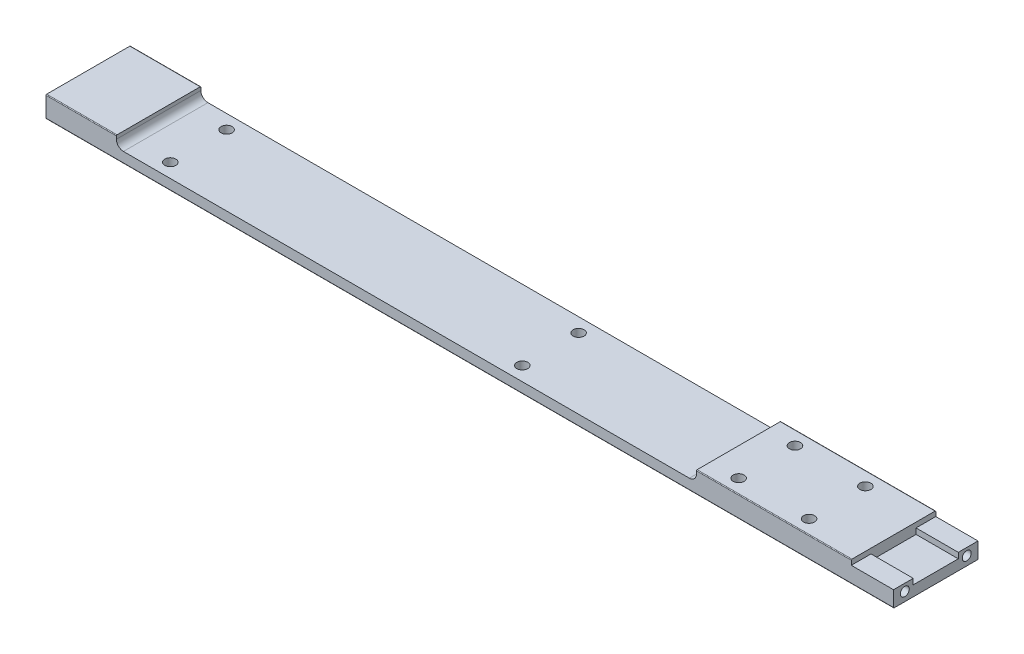
SolidWorks part; units mm, degrees
material "6061 Alloy"
ref_plane "Front Plane" through (0, 0, 0) normal (0, 0, 1) x (1, 0, 0)
ref_plane "Top Plane" through (0, 0, 0) normal (0, 1, 0) x (1, 0, 0)
ref_plane "Right Plane" through (0, 0, 0) normal (1, 0, 0) x (0, 0, -1)
sketch "Sketch1" plane through (0, 0, 0) normal (0, 1, 0) x (1, 0, 0)
  line L1 (191.135, -19.05) -> (-191.135, -19.05)
  line L2 (191.135, -19.05) -> (191.135, 19.05)
  line L3 (191.135, 19.05) -> (-191.135, 19.05)
  line L4 (-191.135, -19.05) -> (-191.135, 19.05)
  line L5 (191.135, -19.05) -> (-191.135, 19.05) construction
  line L6 (191.135, 19.05) -> (-191.135, -19.05) construction
  point P0 (0, 0)
  dimension "Length" = 382.27
  dimension "Width" = 38.1
sketch "Sketch2" plane through (0, 0, 0) normal (1, 0, 0) x (0, 0, -1)
  line L0 (19.05, 4.7625) -> (19.05, -4.7625) construction
  point P2 (19.05, 0)
  dimension "Thickness" = 9.525
sketch "Sketch3" plane through (0, 0, 0) normal (0, 1, 0) x (1, 0, 0)
  line L1 (-191.135, 19.05) -> (191.135, 19.05)
  line L2 (-191.135, 19.05) -> (-191.135, -19.05)
  line L3 (-191.135, -19.05) -> (191.135, -19.05)
  line L4 (191.135, 19.05) -> (191.135, -19.05)
extrude "Boss-Extrude1" add sketch "Sketch3" against normal up to vertex (4.7625 mm away) and the other way up to vertex (4.7625 mm away) up to point (0, -4.7625, -19.05) other way up to point (0, 4.7625, -19.05)
fillet "Fillet1" radius 0.3143 4 edges at (0, -4.7625, 19.05) (0, -4.7625, -19.05) (0, 4.7625, -19.05) (0, 4.7625, 19.05)
sketch "Sketch4" plane through (-191.135, 0, 0) normal (-1, 0, 0) x (0, 0, 1)
  line L0 (0, -0.762) -> (13.97, -0.762) construction
  line L1 (0, -0.762) -> (-13.97, -0.762) construction
  line L2 (0, -0.762) -> (0, 0) construction
  dimension "D1" = 13.97
  dimension "D2" = 13.97
  dimension "D3" = 0.762
hole_wizard "Tap Drill for #10-32 Tap1" positions "Sketch5" profile "Sketch6" hole size "#10-32" standard "ANSI Inch"
sketch "Sketch5" plane through (-191.135, 0, 0) normal (-1, 0, 0) x (0, 0, 1)
  point P0 (-13.97, -0.762)
  point P3 (13.97, -0.762)
sketch "Sketch6" plane through (-191.135, -0.762, -13.97) normal (0, 1, 0) x (0, 0, 1)
  line L0 (0, 0) -> (0, 26.6133)
  line L1 (0, 26.6133) -> (2.0193, 25.4)
  line L2 (2.0193, 25.4) -> (2.0193, 0)
  line L5 (2.0193, 0) -> (0, 0)
  line L10 (0, 26.6133) -> (-2.0193, 25.4) construction
  line L11 (0, -6.35) -> (0, 107.95) construction
  dimension "Hole Dia." = 4.0386
  dimension "Hole Depth" = 25.4
  dimension "Drill Angle" = 118
hole_wizard "Tap Drill for #10-32 Tap2" positions "Sketch7" profile "Sketch8" hole size "#10-32" standard "ANSI Inch"
sketch "Sketch7" plane through (191.135, 0, 0) normal (1, 0, 0) x (0, 0, -1)
  point P0 (-13.97, -0.762)
  point P3 (13.97, -0.762)
sketch "Sketch8" plane through (191.135, -0.762, 13.97) normal (0, 1, 0) x (0, 0, -1)
  line L0 (0, 0) -> (0, 26.6133)
  line L1 (0, 26.6133) -> (2.0193, 25.4)
  line L2 (2.0193, 25.4) -> (2.0193, 0)
  line L5 (2.0193, 0) -> (0, 0)
  line L10 (0, 26.6133) -> (-2.0193, 25.4) construction
  line L11 (0, -6.35) -> (0, 107.95) construction
  dimension "Hole Dia." = 4.0386
  dimension "Hole Depth" = 25.4
  dimension "Drill Angle" = 118
sketch "Sketch10" plane through (0, 0, -19.05) normal (0, 0, -1) x (-1, 0, 0)
  line L0 (159.385, 4.7625) -> (159.385, 3.175)
  line L1 (-191.135, 4.7625) -> (191.135, 4.7625) construction
  line L2 (156.21, 0) -> (-99.06, 0)
  line L3 (-102.235, 3.175) -> (-102.235, 4.7625)
  line L4 (-102.235, 4.7625) -> (159.385, 4.7625)
  line L5 (-191.135, -4.7625) -> (-191.135, 78.8029) construction
  line L6 (191.135, -4.7625) -> (191.135, 78.8029) construction
  line L7 (-191.135, 4.7625) -> (-172.085, 4.7625)
  line L8 (-172.085, 4.7625) -> (-172.085, 2.4765)
  line L9 (-172.085, 2.4765) -> (-191.135, 2.4765)
  line L10 (-191.135, -4.4482) -> (-191.135, 4.4482) construction
  line L11 (-191.135, 2.4765) -> (-191.135, 4.7625)
  arc A0 (159.385, 3.175) -> (156.21, 0) centre (156.21, 3.175) cw
  arc A1 (-99.06, 0) -> (-102.235, 3.175) centre (-99.06, 3.175) cw
  point P12 (159.385, 0)
  dimension "D4" = 3.175
  dimension "D1" = 88.9
  dimension "D2" = 31.75
  dimension "D3" = 4.7625
  dimension "D5" = 19.05
  dimension "D6" = 2.286
extrude "Cut-Extrude1" cut sketch "Sketch10" against normal through all
sketch "Sketch13" plane through (0, -4.7625, 0) normal (0, -1, 0) x (1, 0, 0)
  line L0 (191.135, 0) -> (146.685, 0) construction
  line L1 (191.135, 18.7357) -> (191.135, -18.7357) construction
  line L2 (146.685, 0) -> (146.685, 12.7) construction
  line L3 (146.685, 12.7) -> (114.935, 12.7) construction
  line L4 (114.935, 12.7) -> (114.935, -12.7) construction
  line L5 (114.935, -12.7) -> (146.685, -12.7) construction
  line L6 (146.685, -12.7) -> (146.685, 0) construction
  dimension "D1" = 44.45
  dimension "D2" = 31.75
  dimension "D3" = 31.75
hole_wizard "#10 Clearance Hole1" positions "Sketch14" profile "Sketch15" hole size "#10" standard "ANSI Inch" end condition through all
sketch "Sketch14" plane through (0, -4.7625, 0) normal (0, -1, 0) x (-1, 0, 0)
  point P0 (-114.935, 12.7)
  point P3 (-146.685, 12.7)
  point P6 (-146.685, -12.7)
  point P9 (-114.935, -12.7)
sketch "Sketch15" plane through (114.935, -4.7625, -12.7) normal (1, 0, 0) x (0, 0, -1)
  line L0 (0, 0) -> (0, 9.525)
  line L1 (0, 9.525) -> (2.4892, 9.525)
  line L2 (2.4892, 9.525) -> (2.4892, 3.1411)
  line L3 (2.4892, 3.1411) -> (5.2197, 0)
  line L5 (5.2197, 0) -> (0, 0)
  line L6 (-2.4892, 3.1411) -> (-5.2197, 0) construction
  line L11 (0, -6.35) -> (0, 107.95) construction
  dimension "Thru Hole Dia." = 4.9784
  dimension "Thru Hole Depth" = 9.525
  dimension "Near C'Sink Dia." = 10.4394
  dimension "Near C'Sink Angle" = 82
sketch "Sketch17" plane through (0, 2.4765, 0) normal (0, 1, 0) x (1, 0, 0)
  line L23 (191.135, 0) -> (191.135, 10.16)
  line L24 (191.135, -19.05) -> (191.135, 19.05) construction
  line L25 (191.135, 10.16) -> (172.085, 10.16)
  line L26 (172.085, -19.05) -> (172.085, 19.05) construction
  line L27 (172.085, 10.16) -> (172.085, -10.16)
  line L28 (172.085, -10.16) -> (191.135, -10.16)
  line L29 (191.135, -10.16) -> (191.135, 0)
extrude "Cut-Extrude2" cut sketch "Sketch17" against normal blind 2.54
sketch "Sketch18" plane through (0, 0, 0) normal (0, 1, 0) x (1, 0, 0)
  line L0 (30.0312, 19.05) -> (17.3312, 19.05) construction
  line L1 (99.06, 19.05) -> (-156.21, 19.05) construction
  line L2 (30.0312, 19.584) -> (30.0312, 16.7333) construction
  line L3 (17.3312, 19.05) -> (17.3312, 12.7) construction
  line L4 (17.3312, 12.7) -> (17.3312, -12.7) construction
  line L5 (17.3312, -12.7) -> (17.3312, -19.05) construction
  line L6 (99.06, -19.05) -> (-156.21, -19.05) construction
  line L7 (17.3312, -19.05) -> (-141.4188, -19.05) construction
  line L8 (-141.4188, -19.05) -> (-141.4188, -12.7) construction
  line L9 (-141.4188, -12.7) -> (-141.4188, 12.7) construction
  line L10 (-141.4188, 12.7) -> (-141.4188, 19.05) construction
  dimension "D1" = 6.35
  dimension "D2" = 25.4
  dimension "D3" = 6.35
  dimension "D4" = 25.4
hole_wizard "#10 Clearance Hole2" positions "Sketch19" profile "Sketch20" hole size "#10" standard "ANSI Inch" end condition through all
sketch "Sketch19" plane through (0, 0, 0) normal (0, 1, 0) x (1, 0, 0)
  point P0 (-141.4188, 12.7)
  point P3 (-141.4188, -12.7)
  point P6 (17.3312, 12.7)
  point P9 (17.3312, -12.7)
sketch "Sketch20" plane through (-141.4188, 0, -12.7) normal (1, 0, 0) x (0, 0, 1)
  line L0 (0, 0) -> (0, 4.7625)
  line L1 (0, 4.7625) -> (2.4892, 4.7625)
  line L2 (2.4892, 4.7625) -> (2.4892, 0)
  line L5 (2.4892, 0) -> (0, 0)
  line L11 (0, -6.35) -> (0, 107.95) construction
  dimension "Thru Hole Dia." = 4.9784
  dimension "Thru Hole Depth" = 4.7625
equation "\"D1@Fillet1\" = \"Thickness@Sketch2\" * .033"
